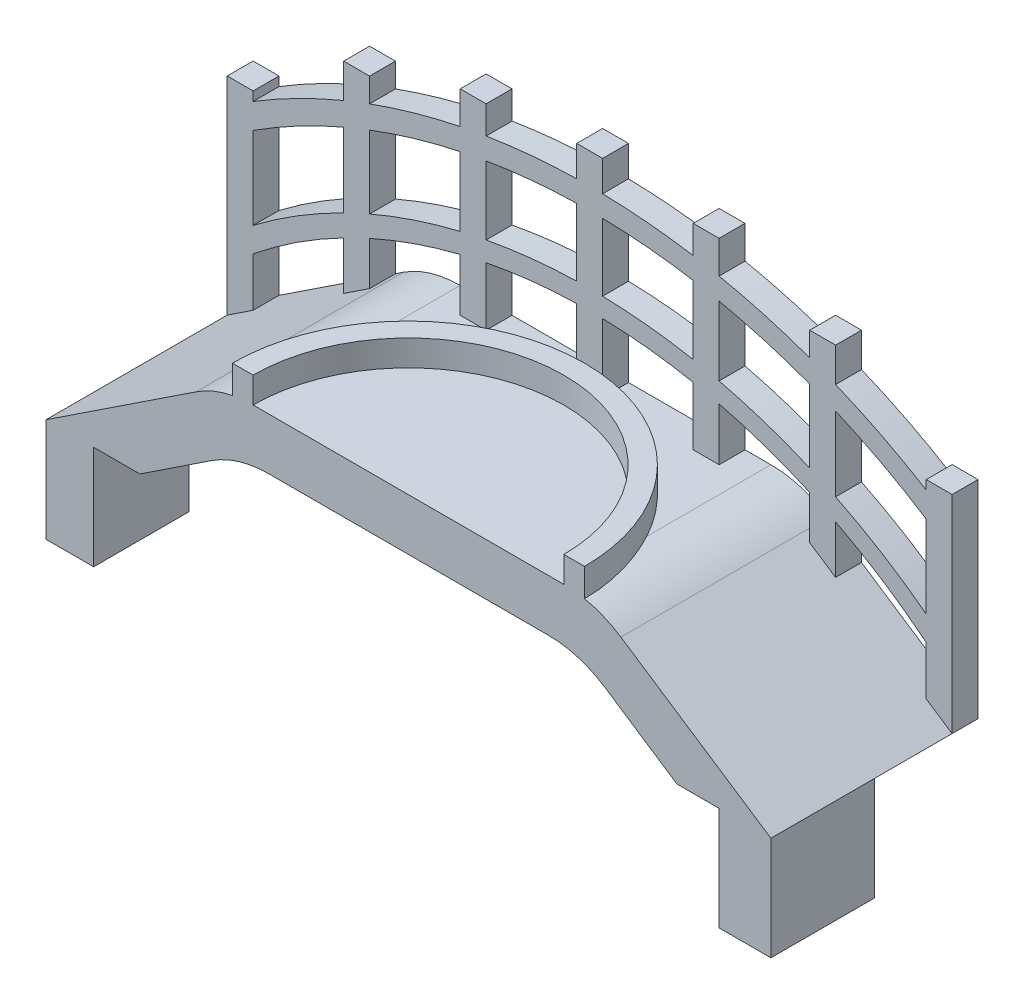
SolidWorks part; units mm, degrees
ref_plane "Front Plane" through (0, 0, 0) normal (0, 0, 1) x (1, 0, 0)
ref_plane "Top Plane" through (0, 0, 0) normal (0, 1, 0) x (1, 0, 0)
ref_plane "Right Plane" through (0, 0, 0) normal (1, 0, 0) x (0, 0, -1)
sketch "Sketch5" plane through (0, 0, 0) normal (0, 0, 1) x (1, 0, 0)
  line L0 (1.751, -2.6485) -> (10.1527, 2.906)
  line L1 (12.7, 7.134) -> (31.75, 7.134)
  line L2 (0, 0) -> (9.198, 6.081)
  line L3 (35.252, 6.081) -> (44.45, 0)
  line L4 (0, 0) -> (10.7907, 0) construction
  line L5 (44.45, 0) -> (33.6593, 0) construction
  line L6 (13.6546, 3.959) -> (30.7954, 3.959)
  line L7 (34.2973, 2.906) -> (42.699, -2.6485)
  line L8 (0, 0) -> (5.7571, 0)
  line L9 (44.45, 0) -> (38.6929, 0)
  line L10 (0, 0) -> (0, 9.525)
  line L11 (44.45, 0) -> (44.45, 9.525)
  line L12 (22.225, 7.134) -> (22.225, 16.659) construction
  line L13 (22.225, 7.134) -> (22.225, 3.959) construction
  line L14 (0, 0) -> (1.5875, 0)
  line L15 (0, 0) -> (0, 12.7)
  line L16 (0, 12.7) -> (1.5875, 12.7)
  line L17 (1.5875, 0) -> (1.5875, 12.7)
  line L18 (23.0187, 3.959) -> (21.4312, 3.959)
  line L19 (23.0187, 3.959) -> (23.0188, 19.834)
  line L20 (23.0188, 19.834) -> (21.4312, 19.834)
  line L21 (21.4312, 3.959) -> (21.4312, 19.834)
  line L22 (1.5875, 9.2118) -> (7.1438, 9.2118) construction
  line L23 (7.1437, 17.0604) -> (8.7312, 17.0604)
  line L24 (7.1437, 17.0604) -> (7.1438, 1.1854)
  line L25 (7.1438, 1.1854) -> (8.7313, 1.1854)
  line L26 (8.7312, 17.0604) -> (8.7313, 1.1854)
  line L27 (14.2875, 19.1598) -> (15.875, 19.1598)
  line L28 (14.2875, 19.1598) -> (14.2875, 3.2848)
  line L29 (14.2875, 3.2848) -> (15.875, 3.2848)
  line L30 (15.875, 19.1598) -> (15.875, 3.2848)
  line L31 (8.7313, 8.208) -> (14.2875, 8.208) construction
  line L32 (15.875, 13.1596) -> (21.4312, 13.1596) construction
  line L33 (7.9375, 17.0604) -> (7.9375, 13.8854) construction
  line L34 (15.0812, 19.1598) -> (15.0812, 15.9848) construction
  line L35 (44.45, 0) -> (38.6929, 0)
  line L36 (30.1625, 19.1598) -> (28.575, 19.1598)
  line L37 (30.1625, 19.1598) -> (30.1625, 3.2848)
  line L38 (28.575, 19.1598) -> (28.575, 3.2848)
  line L39 (30.1625, 3.2848) -> (28.575, 3.2848)
  line L40 (37.3062, 1.1854) -> (35.7187, 1.1854)
  line L41 (37.3062, 17.0604) -> (35.7187, 17.0604)
  line L42 (35.7187, 17.0604) -> (35.7187, 1.1854)
  line L43 (37.3062, 17.0604) -> (37.3062, 1.1854)
  line L44 (44.45, 12.7) -> (42.8625, 12.7)
  line L45 (44.45, 0) -> (44.45, 12.7)
  line L46 (44.45, 0) -> (44.45, 9.525)
  line L47 (42.8625, 0) -> (42.8625, 12.7)
  line L48 (11.7454, 3.959) -> (32.7046, 3.959) construction
  line L49 (32.7046, 3.959) -> (42.699, -2.6485) construction
  line L50 (10.7907, 7.134) -> (33.6593, 7.134) construction
  line L51 (33.6593, 7.134) -> (44.45, 0) construction
  line L52 (1.751, -2.6485) -> (11.7454, 3.959) construction
  line L53 (0, 0) -> (10.7907, 7.134) construction
  arc A0 (0, 9.525) -> (44.45, 9.525) centre (22.225, -21.5277) cw
  arc A1 (0, 11.1125) -> (44.45, 11.1125) centre (22.225, -21.5277) cw
  arc A2 (30.7954, 3.959) -> (34.2973, 2.906) centre (30.7954, -2.391) cw
  arc A3 (31.75, 7.134) -> (35.252, 6.081) centre (31.75, 0.784) cw
  arc A4 (10.1527, 2.906) -> (13.6546, 3.959) centre (13.6546, -2.391) cw
  arc A5 (12.7, 7.134) -> (9.198, 6.081) centre (12.7, 0.784) ccw
  point P65 (33.6593, 7.134)
  dimension "D12" = 6.35
  dimension "D2" = 19.05
  dimension "D1" = 44.45
  dimension "D3" = 3.175
  dimension "D4" = 9.525
  dimension "D5" = 1.5875
  dimension "D6" = 12.7
  dimension "D7" = 1.5875
  dimension "D8" = 15.875
  dimension "D9" = 12.7
  dimension "D10" = 3.175
  dimension "D11" = 1.5875
extrude "Boss-Extrude1" add sketch "Sketch5" along normal blind 12.7 contours L8 L17 L2 | L25 L24 L2 L17 L8 L0 | L26 L2 L24 L25 L0 | L1 A5 L2 L26 L0 A4 L6 L28 | L30 L1 L28 L6 | L1 L30 L6 L21 | L21 L6 L19 L1 | L38 L1 L19 L6 | L1 L38 L6 L37 | A3 L1 L37 L6 A2 L7 L42 L3 | L43 L3 L42 L7 L40 | L35 L47 L3 L43 L40 L7 | L47 L9 L3 region at (4.8921, 1.6908, 0) region at (7.9435, 3.3651, 0) region at (1.0583, 0.3498, 0) region at (11.4022, 5.0552, 0) region at (15.0812, 5.5465, 0) region at (18.6531, 5.5465, 0) region at (22.225, 5.5465, 0) region at (25.7969, 5.5465, 0) region at (29.3687, 5.5465, 0) region at (33.0478, 5.0552, 0) region at (36.5065, 3.3651, 0) region at (39.5579, 1.6908, 0) region at (43.3917, 0.3498, 0)
extrude "Boss-Extrude2" add sketch "Sketch5<4>" along normal blind 1.5875 separate body contours A1 L15 A0 L17 | A1 L17 A0 L24 | A1 L24 A0 L26 | A1 L26 A0 L28 | A1 L28 A0 L30 | A1 L30 A0 L21 | A1 L21 A0 L19 | A1 L19 A0 L38 | A1 L38 A0 L37 | A1 L37 A0 L42 | A1 L42 A0 L43 | A1 L43 A0 L47 | A1 L47 A0 L45 region at (0.7895, 10.851, 0) region at (4.3267, 12.8905, 0) region at (7.9352, 14.5811, 0) region at (11.4895, 15.7587, 0) region at (15.0802, 16.6439, 0) region at (18.647, 17.111, 0) region at (22.225, 17.3071, 0) region at (25.803, 17.111, 0) region at (29.3698, 16.6439, 0) region at (32.9605, 15.7587, 0) region at (36.5148, 14.5811, 0) region at (40.1233, 12.8905, 0) region at (43.6605, 10.851, 0)
sketch "Sketch5<4>" plane through (0, 0, 0) normal (0, 0, 1) x (1, 0, 0) same geometry as "Sketch5"
extrude "Boss-Extrude6" add sketch "Sketch5<7>" along normal blind 1.5875 contours L15 A1 L17 L16 | A0 L10 L2 L17 | A1 L15 A0 L17 | A0 L24 L2 L26 | L24 A1 L26 L23 | L26 L2 L24 L0 | L26 L0 L24 L25 | A1 L24 A0 L26 | L28 A1 L30 L27 | A1 L28 A0 L30 | A0 L28 L1 L30 | L30 L1 L28 L6 | L30 L6 L28 L29 | L21 L18 L19 L6 | L21 L6 L19 L1 | A0 L21 L1 L19 | L21 A1 L19 L20 | A1 L21 A0 L19 | L38 A1 L37 L36 | A0 L38 L1 L37 | L1 L38 L6 L37 | L39 L37 L6 L38 | L43 L7 L42 L40 | L43 L3 L42 L7 | A0 L42 L3 L43 | A1 L42 A0 L43 | L42 A1 L43 L41 | L47 A1 L45 L44 | A1 L47 A0 L45 | A0 L47 L3 L11 | L47 L9 L3 region at (7.9435, 3.3651, 0) region at (8.3375, 1.4457, 0) region at (0.7941, 5.2992, 0) region at (7.9312, 9.5615, 0) region at (0.7895, 10.851, 0) region at (7.9352, 14.5811, 0) region at (0.6663, 12.1261, 0) region at (15.0812, 5.5465, 0) region at (15.0812, 3.6219, 0) region at (7.8917, 16.1623, 0) region at (15.0858, 11.5584, 0) region at (15.0802, 16.6439, 0) region at (15.0604, 18.2312, 0) region at (22.225, 5.5465, 0) region at (22.225, 11.8951, 0) region at (22.225, 17.3071, 0) region at (22.225, 18.896, 0) region at (29.3687, 5.5465, 0) region at (29.3687, 3.6219, 0) region at (29.3642, 11.5584, 0) region at (29.3896, 18.2312, 0) region at (36.5188, 9.5615, 0) region at (36.5148, 14.5811, 0) region at (36.5583, 16.1623, 0) region at (36.5065, 3.3651, 0) region at (36.1125, 1.4457, 0) region at (43.6559, 5.2992, 0) region at (43.6605, 10.851, 0) region at (43.7837, 12.1261, 0) region at (43.3917, 0.3498, 0)
sketch "Sketch5<7>" plane through (0, 0, 0) normal (0, 0, 1) x (1, 0, 0) same geometry as "Sketch5"
sketch "Sketch6" plane through (0, 0, 0) normal (0, 0, -1) x (-1, 0, 0)
  line L0 (-44.45, 0) -> (-44.45, 12.7) construction
  line L1 (0, 0) -> (0, 12.7) construction
  line L2 (-44.45, 4.2704) -> (-44.45, 2.6829)
  line L3 (0, 2.6829) -> (0, 4.2704)
  arc A0 (-44.45, 4.2704) -> (0, 4.2704) centre (-22.225, -21.5277) cw
  arc A1 (-44.45, 2.6829) -> (0, 2.6829) centre (-22.225, -21.5277) cw
  arc A2 (-23.0187, 16.6507) -> (-28.575, 16.1273) centre (-22.225, -21.5277) ccw construction
  dimension "D1" = 1.5875
extrude "Boss-Extrude7" add sketch "Sketch6" against normal blind 1.5875
sketch "Sketch11" plane through (0, 7.134, 0) normal (0, 1, 0) x (1, 0, 0)
  line L1 (11.43, -12.7) -> (33.02, -12.7)
  circle A0 centre (22.225, -12.7) radius 9.525
  circle A1 centre (22.225, -12.7) radius 10.795
  line M9 (31.75, -12.7) -> (31.75, 0)
  line M19 (12.7, 0) -> (12.7, -12.7)
  dimension "D1" = 19.05
  dimension "D2" = 21.59
extrude "Boss-Extrude9" add sketch "Sketch11" along normal blind 1.5875 and the other way blind 0.254 contours A1 A0 M9 M19 | A1 L1 M19 | L1 A1 M9 region at (12.1893, 7.134, 10.7791) region at (12.919, 7.134, 10.16) region at (32.2607, 7.134, 10.7791)
sketch "Sketch12" plane through (0, 0, 0) normal (0, -1, 0) x (1, 0, 0)
  line L1 (0, 12.7) -> (2.921, 12.7)
  line L2 (0, 12.7) -> (0, 6.858)
  line L3 (0, 6.858) -> (2.921, 6.858)
  line L4 (2.921, 12.7) -> (2.921, 6.858)
  line L5 (44.45, 12.7) -> (41.275, 12.7)
  line L6 (44.45, 12.7) -> (44.45, 6.35)
  line L7 (44.45, 6.35) -> (41.275, 6.35)
  line L8 (41.275, 12.7) -> (41.275, 6.35)
  dimension "D1" = 2.921
  dimension "D2" = 5.842
  dimension "D3" = 6.35
  dimension "D4" = 3.175
extrude "Boss-Extrude10" add sketch "Sketch12" along normal blind 6.35
sketch "Sketch14" plane through (0, 0, 12.7) normal (0, 0, 1) x (1, 0, 0)
